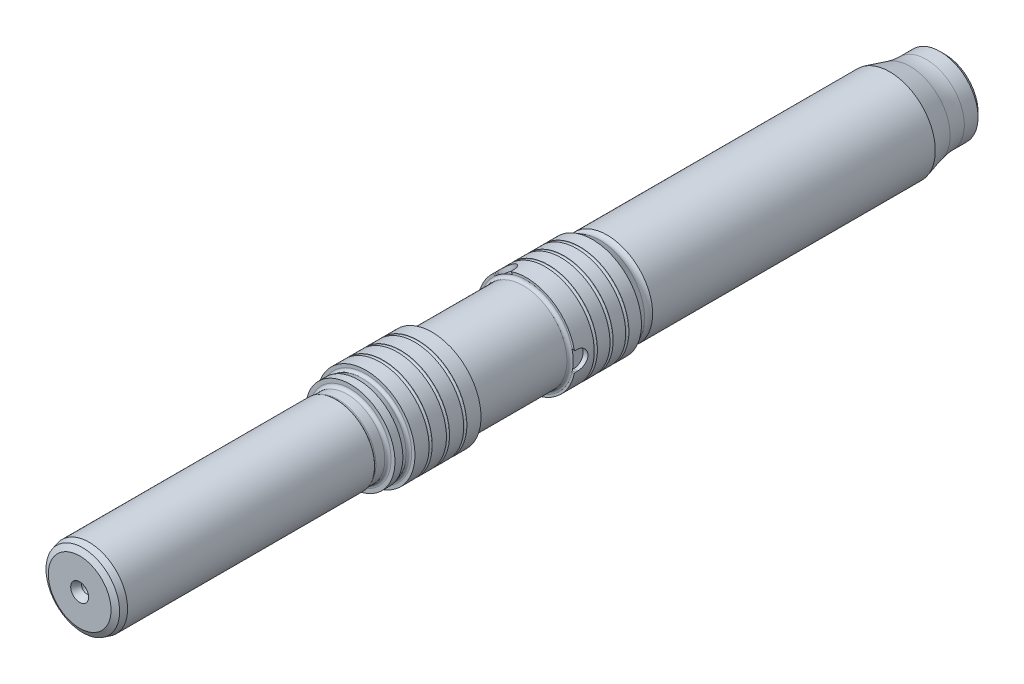
SolidWorks part; units mm, degrees
material "EN39B"
ref_plane "Front Plane" through (0, 0, 0) normal (0, 0, 1) x (1, 0, 0)
ref_plane "Top Plane" through (0, 0, 0) normal (0, 1, 0) x (1, 0, 0)
ref_plane "Right Plane" through (0, 0, 0) normal (1, 0, 0) x (0, 0, -1)
sketch "Sketch1" plane through (0, 0, 0) normal (1, 0, 0) x (0, 0, -1)
  line L0 (0, 0) -> (-275, 0) construction
  line L1 (-17.5, 14.4875) -> (-107.3516, 14.4875)
  line L2 (0, 2.85) -> (0, 10.575)
  line L3 (-274, 11.7016) -> (-275, 9.9696)
  line L4 (-133, 14.875) -> (-133, 15.5775)
  line L5 (-163, 14.875) -> (-163, 15.5775)
  line L6 (-184, 14.55) -> (-184, 15.5775)
  line L7 (-189, 12.9925) -> (-189, 14.2325)
  line L8 (-112, 15.5775) -> (-116, 15.5775)
  line L9 (-163, 15.5775) -> (-167.5, 15.5775)
  line L10 (-184, 0.0483) -> (-184, 31.9032) construction
  line L11 (-163, 0.0483) -> (-163, 31.9032) construction
  line L12 (-189, 0.0483) -> (-189, 31.9032) construction
  line L13 (-133, 0.0483) -> (-133, 31.9032) construction
  line L14 (-272, 12.2375) -> (-274, 11.7016)
  line L15 (0, 15.5775) -> (-275, 15.5775) construction
  line L16 (-193.5, 12.2375) -> (-272, 12.2375)
  line L17 (-134, 13.875) -> (-162, 13.875)
  line L18 (0, 14.4875) -> (-275, 14.4875) construction
  line L19 (-275, 9.9696) -> (-275, 2.85)
  line L20 (0, 13.875) -> (-275, 13.875) construction
  line L21 (0, 12.2375) -> (-275, 12.2375) construction
  line L22 (-186.5, 14.2325) -> (-189, 14.2325)
  line L23 (-190, 11.9925) -> (-192.8443, 11.9925)
  line L24 (-112, 15.5775) -> (-109.6885, 14.2429)
  line L25 (-117, 15.5775) -> (-121, 15.5775)
  line L26 (0, 11.9925) -> (-275, 11.9925) construction
  line L27 (-275, 2.85) -> (-272.7916, 1.575)
  line L28 (-179.5, 15.5775) -> (-179.5, 15.45)
  line L29 (-5.8634, 12.075) -> (-1.5, 12.075)
  line L30 (-178.5, 15.5775) -> (-178.5, 15.45)
  line L31 (-122, 15.5775) -> (-126, 15.5775)
  line L32 (-272.7916, 1.575) -> (-269, 1.575)
  line L33 (-126.5, 14.95) -> (-126.5, 15.45) construction
  line L34 (-179.5, 15.5775) -> (-184, 15.5775)
  line L35 (-174, 15.5775) -> (-174, 15.45)
  line L36 (-121.5, 14.95) -> (-121.5, 15.45) construction
  line L37 (-116.5, 14.95) -> (-116.5, 15.45) construction
  line L38 (-126.5, 14.875) -> (-126.5, 15.5775) construction
  line L39 (-121.5, 14.875) -> (-121.5, 15.5775) construction
  line L40 (-116.5, 14.875) -> (-116.5, 15.5775) construction
  line L41 (-127, 15.5775) -> (-133, 15.5775)
  line L42 (-173, 15.5775) -> (-173, 15.45)
  line L43 (-168.5, 15.5775) -> (-168.5, 15.45)
  line L44 (-167.5, 15.5775) -> (-167.5, 15.45)
  line L45 (-174, 15.5775) -> (-178.5, 15.5775)
  line L46 (-168.5, 15.5775) -> (-173, 15.5775)
  line L47 (-127, 15.45) -> (-127, 15.5775)
  line L48 (-126, 15.45) -> (-126, 15.5775)
  line L49 (-122, 15.45) -> (-122, 15.5775)
  line L50 (-269, 1.575) -> (-268.0536, 0)
  line L51 (0, 2.85) -> (-2.2084, 1.575)
  line L52 (-2.2084, 1.575) -> (-6, 1.575)
  line L53 (-6, 1.575) -> (-6.9464, 0)
  line L54 (-268.0536, 0) -> (-6.9464, 0)
  line L55 (-186.5, 14.2325) -> (-185.0336, 13.7849)
  line L56 (-121, 15.45) -> (-121, 15.5775)
  line L57 (-117, 15.45) -> (-117, 15.5775)
  line L58 (-116, 15.45) -> (-116, 15.5775)
  line L59 (-1.5, 12.075) -> (0, 10.575)
  line L60 (-17.5, 14.4875) -> (-11.0398, 12.7565)
  arc A0 (-193.5, 12.2375) -> (-192.8443, 11.9925) centre (-192.8443, 12.9925) ccw
  arc A1 (-185.0336, 13.7849) -> (-184, 14.55) centre (-184.8, 14.55) ccw
  arc A2 (-189, 12.9925) -> (-190, 11.9925) centre (-190, 12.9925) cw
  arc A3 (-11.0398, 12.7565) -> (-5.8634, 12.075) centre (-5.8634, 32.075) ccw
  arc A4 (-109.6885, 14.2429) -> (-107.3516, 14.4875) centre (-108.6885, 15.975) ccw
  arc A5 (-179.5, 15.45) -> (-178.5, 15.45) centre (-179, 15.45) ccw
  arc A6 (-134, 13.875) -> (-133, 14.875) centre (-134, 14.875) ccw
  arc A7 (-162, 13.875) -> (-163, 14.875) centre (-162, 14.875) cw
  arc A8 (-127, 15.45) -> (-126, 15.45) centre (-126.5, 15.45) ccw
  arc A9 (-122, 15.45) -> (-121, 15.45) centre (-121.5, 15.45) ccw
  arc A10 (-117, 15.45) -> (-116, 15.45) centre (-116.5, 15.45) ccw
  arc A11 (-174, 15.45) -> (-173, 15.45) centre (-173.5, 15.45) ccw
  arc A12 (-168.5, 15.45) -> (-167.5, 15.45) centre (-168, 15.45) ccw
  point P5 (-112, 0)
  point P6 (0, 31.855)
  point P7 (-112, 31.855)
  point P29 (0, 14.23)
  point P30 (-112, 14.485)
  point P32 (-275, 14.23)
  point P42 (-17.5, 0)
  point P45 (0, 12.075)
  point P46 (-275, 12.075)
  point P50 (-17.5, 13.975)
  point P53 (-112, 13.975)
  point P65 (-275, 11.4337)
  point P67 (0, 14.75)
  point P68 (-275, 14.75)
  point P106 (0, 12.075)
  dimension "D8" = 30
  dimension "D9" = 2
  dimension "D10" = 1
  dimension "D30" = 27.5
  dimension "D34" = 2.5
  dimension "D35" = 11.5
  dimension "D38" = 0.5
  dimension "D40" = 29.9
  dimension "D41" = 3.15
  dimension "D42" = 0.5
  dimension "D48" = 16
  dimension "D49" = 29.9
  dimension "D33" = 0.8
  dimension "D16" = 20
  dimension "D43" = 5.7
  dimension "D44" = 86
  dimension "D47" = 1
  dimension "D13" = 15
  dimension "D12" = 24.15
  dimension "D37" = 29.9
  dimension "D39" = 29.9
  dimension "D28" = 1
  dimension "D1" = 275
  dimension "D7" = 28.975
  dimension "D11" = 17.5
  dimension "D14" = 112
  dimension "D15" = 27.95
  dimension "D17" = 31.155
  dimension "D18" = 27.75
  dimension "D19" = 24.475
  dimension "D20" = 15
  dimension "D21" = 3
  dimension "D22" = 1
  dimension "D23" = 45
  dimension "D24" = 21
  dimension "D25" = 6.5
  dimension "D26" = 21
  dimension "D27" = 5
  dimension "D29" = 28.465
  dimension "D31" = 23.985
  dimension "D32" = 4.5
  dimension "D36" = 16.5
  dimension "D45" = 5
  dimension "D46" = 10.5
  dimension "D50" = 3.15
  dimension "D51" = 59
  dimension "D54" = 30
  dimension "D55" = 6
  dimension "D56" = 30
  dimension "D57" = 59
  dimension "D58" = 5.7
  dimension "D60" = 6
  dimension "D62" = 91
revolve "Revolve1" add sketch "Sketch1" angle 360 about L0
ref_plane "Plane2" through (15.5787, 0, 0) normal (1, 0, 0) x (0, 0, -1)
sketch "Sketch3" plane through (15.5787, 0, 0) normal (1, 0, 0) x (0, 0, -1)
  line L1 (-133, 15.5775) -> (-133, -15.5775) construction
  line L2 (-133, 14.875) -> (-133, -14.875) construction
  line L4 (-132, 3) -> (-132.7, 3)
  line L5 (-132.7, -3) -> (-132, -3)
  line L6 (-133, -3.3) -> (-133, 3.3)
  arc A3 (-132, 3) -> (-132, -3) centre (-132, 0) cw
  arc A4 (-132.7, -3) -> (-133, -3.3) centre (-132.7, -3.3) ccw
  arc A5 (-132.7, 3) -> (-133, 3.3) centre (-132.7, 3.3) cw
  point P16 (-133, 0)
  dimension "D2" = 3
  dimension "D3" = 4
  dimension "D1" = 0.3
  dimension "D4" = 0.3
  dimension "D5" = 6.6
extrude "Cut-Extrude1" cut sketch "Sketch3" against normal blind 1.55
pattern_circular "CirPattern1" count 3 over 360 of "Cut-Extrude1"
